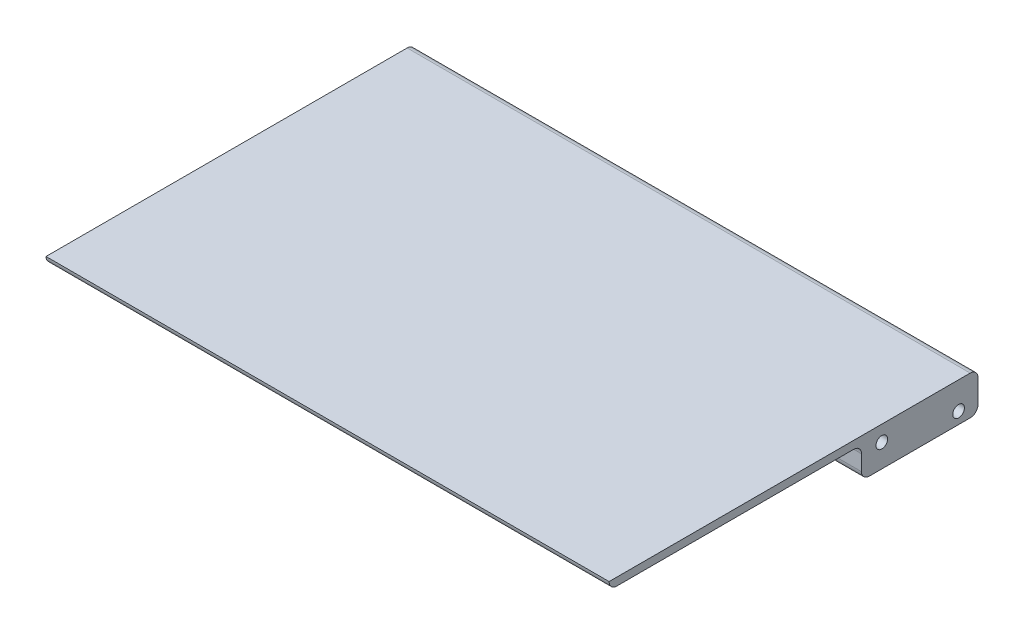
SolidWorks part; units mm, degrees
material "ABS"
ref_plane "前视基准面" through (0, 0, 0) normal (0, 0, 1) x (1, 0, 0)
ref_plane "上视基准面" through (0, 0, 0) normal (0, 1, 0) x (1, 0, 0)
ref_plane "右视基准面" through (0, 0, 0) normal (1, 0, 0) x (0, 0, -1)
other "Configuration Table"
sketch "草图1" plane through (0, 0, 0) normal (0, 1, 0) x (1, 0, 0)
  line L1 (72.5, -47.5) -> (-72.5, -47.5)
  line L2 (72.5, -47.5) -> (72.5, 47.5)
  line L3 (72.5, 47.5) -> (-72.5, 47.5)
  line L4 (-72.5, -47.5) -> (-72.5, 47.5)
  line L5 (72.5, -47.5) -> (-72.5, 47.5) construction
  line L6 (72.5, 47.5) -> (-72.5, -47.5) construction
  point P0 (0, 0)
  dimension "D1" = 145
  dimension "D2" = 95
extrude "凸台-拉伸1" add sketch "草图1" along normal blind 2
sketch "草图2" plane through (72.5, 0, 0) normal (1, 0, 0) x (0, 0, -1)
  line L0 (47.5, 0) -> (47.5, -8)
  line L1 (47.5, -8) -> (17.5, -8)
  line L2 (17.5, -8) -> (17.5, 0)
  line L3 (-47.5, 0) -> (47.5, 0) construction
  line L4 (17.5, 0) -> (47.5, 0)
  line L5 (22.7197, -2.0438) -> (42.5, -5) construction
  circle A0 centre (22.7197, -2.0438) radius 1.5
  circle A1 centre (42.5, -5) radius 1.5
  dimension "D1" = 3
  dimension "D2" = 20
  dimension "D3" = 8.5
  dimension "D4" = 30
  dimension "D5" = 8
  dimension "D6" = 3
  dimension "D7" = 5
extrude "凸台-拉伸2" add sketch "草图2" against normal through all
fillet "圆角1" radius 2 5 edges at (0, 2, -47.5) (0, -8, -47.5) (0, -8, -17.5) (0, 0, -17.5) (0, 0, 47.5)
sketch "草图3" plane through (0, -8, 0) normal (0, -1, 0) x (1, 0, 0)
  line L0 (-72.5, -15.5) -> (-72.5, 45.5) construction
  line L1 (62.5, -73.6344) -> (-62.5, -73.6344)
  line L2 (62.5, -73.6344) -> (62.5, 73.6344)
  line L3 (62.5, 73.6344) -> (-62.5, 73.6344)
  line L4 (-62.5, -73.6344) -> (-62.5, 73.6344)
  line L5 (62.5, -73.6344) -> (-62.5, 73.6344) construction
  line L6 (62.5, 73.6344) -> (-62.5, -73.6344) construction
  point P0 (0, 0)
  dimension "D1" = 10
extrude "切除-拉伸2" cut sketch "草图3" against normal up to surface (8 mm away) up to face at (0, 0, 15)
